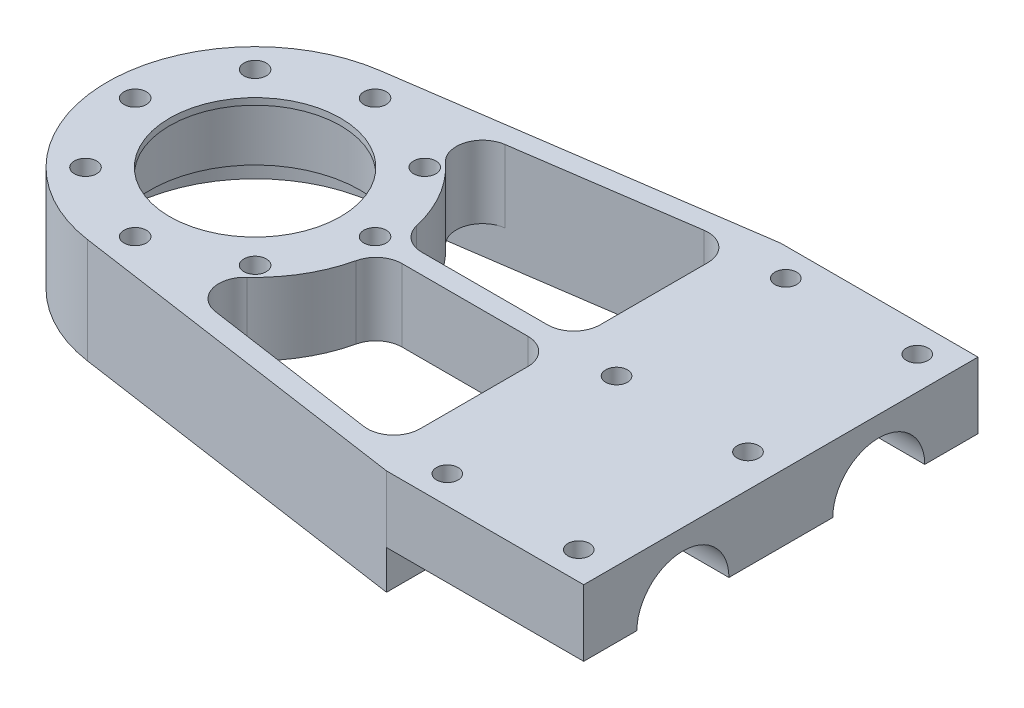
SolidWorks part; units mm, degrees
material "3.1355 (EN-AW 2024)"
ref_plane "Front" through (0, 0, 0) normal (0, 0, 1) x (1, 0, 0)
ref_plane "Top" through (0, 0, 0) normal (0, 1, 0) x (1, 0, 0)
ref_plane "Right" through (0, 0, 0) normal (1, 0, 0) x (0, 0, -1)
sketch "Эскиз1" plane through (0, 0, 0) normal (0, 1, 0) x (1, 0, 0)
  line L0 (0, 0) -> (0, 60)
  line L1 (0, 60) -> (-30, 60)
  line L2 (0, 30) -> (-130, 30) construction
  line L3 (-30, 60) -> (-30, 30) construction
  line L4 (-30, 60) -> (-83.2348, 52.2663)
  line L5 (-30, 0) -> (-83.2348, 7.7337)
  line L6 (0, 0) -> (-30, 0)
  circle A0 centre (-80, 30) radius 22.5 construction
  arc A1 (-83.2348, 52.2663) -> (-83.2348, 7.7337) centre (-80, 30) ccw
  dimension "D2" = 45
  dimension "D1" = 60
  dimension "D3" = 30
  dimension "D4" = 130
  dimension "D5" = 50
extrude "Бобышка-Вытянуть1" add sketch "Эскиз1" along normal blind 16
sketch "Эскиз2" plane through (0, 0, 0) normal (0, -1, 0) x (1, 0, 0)
  circle A0 centre (-80, -30) radius 16
  dimension "D1" = 32
extrude "Вырез-Вытянуть1" cut sketch "Эскиз2" against normal offset from surface (15 mm away) 1 up to face at (-40.9558, 16, -30)
sketch "Эскиз3" plane through (0, 15, 0) normal (0, -1, 0) x (1, 0, 0)
  circle A0 centre (-80, -30) radius 13
  dimension "D1" = 26
extrude "Вырез-Вытянуть2" cut sketch "Эскиз3" against normal through all
sketch "Эскиз4" plane through (0, 0, 0) normal (0, -1, 0) x (1, 0, 0)
  circle A0 centre (-80, -30) radius 20.5
  dimension "D1" = 41
extrude "Вырез-Вытянуть3" cut sketch "Эскиз4" against normal offset from surface (5 mm away) 10 up to face at (-80, 15, -43)
sketch "Эскиз5" plane through (0, 5, 0) normal (0, -1, 0) x (1, 0, 0)
  line L0 (-80, -30) -> (-98.25, -30) construction
  line L1 (-80, -30) -> (-92.9047, -17.0953) construction
  line L2 (-80, -30) -> (-67.0953, -17.0953) construction
  line L3 (-80, -30) -> (-67.0953, -42.9047) construction
  line L4 (-80, -30) -> (-92.9047, -42.9047) construction
  line L5 (-80, -30) -> (-80, -11.75) construction
  line L6 (-80, -30) -> (-61.75, -30) construction
  line L7 (-80, -30) -> (-80, -48.25) construction
  circle A0 centre (-80, -30) radius 18.25 construction
  circle A1 centre (-80, -30) radius 20.5 construction
  point P13 (-80, -30)
  point P17 (-80, -30)
  dimension "D1" = 36.5
  dimension "D2" = 45
  dimension "D3" = 4
  dimension "D4" = 4
hole_wizard "Отверстие с зазором M32" positions "Эскиз19" profile "Эскиз18" hole size "M3" standard "Ansi Metric" end condition through all
sketch "Эскиз19" plane through (0, 5, 0) normal (0, -1, 0) x (-1, 0, 0)
  point P0 (92.9047, 17.0953)
  point P3 (67.0953, 17.0953)
  point P6 (67.0953, 42.9047)
  point P9 (92.9047, 42.9047)
  point P12 (80, 11.75)
  point P15 (61.75, 30)
  point P18 (80, 48.25)
  point P21 (98.25, 30)
sketch "Эскиз18" plane through (-92.9047, 5, -17.0953) normal (1, 0, 0) x (0, 0, -1)
  line L0 (0, 0) -> (0, 11)
  line L1 (0, 11) -> (1.7, 11)
  line L2 (1.7, 11) -> (1.7, 0)
  line L5 (1.7, 0) -> (0, 0)
  line L11 (0, -6.35) -> (0, 107.95) construction
  dimension "Диаметр сквозного отверстия" = 3.4
  dimension "Глубина сквозного отверстия" = 11
sketch "Эскиз8" plane through (0, 0, 0) normal (1, 0, 0) x (0, 0, -1)
  line L0 (30, 16) -> (30, 0) construction
  line L1 (8.1, 5.9) -> (0, 5.9)
  line L2 (0, 16) -> (60, 16) construction
  line L3 (51.9, 5.9) -> (60, 5.9)
  line L4 (22.1, 5.9) -> (37.9, 5.9)
  line L5 (52.5, 0) -> (7.5, 0) construction
  line L6 (0, 16) -> (0, 0) construction
  line L7 (48.667, 0) -> (60, 0)
  line L8 (18.867, 0) -> (41.133, 0)
  line L18 (0, 0) -> (60, 0)
  line L19 (60, 0) -> (60, 16)
  line L20 (60, 16) -> (0, 16)
  line L21 (0, 16) -> (0, 0)
  line L22 (0, 0) -> (11.333, 0)
  line L23 (60, 0) -> (60, 5.9)
  line L25 (0, 5.9) -> (0, 0)
  circle A0 centre (15.1, 5.9) radius 7
  circle A1 centre (44.9, 5.9) radius 7
  line M3 (0, 0) -> (60, 0)
  line M4 (60, 0) -> (60, 16)
  line M6 (0, 16) -> (0, 0)
  dimension "D1" = 14
  dimension "D3" = 10.1
  dimension "D4" = 0
  dimension "D2" = 15.1
extrude "Вырез-Вытянуть8" cut sketch "Эскиз8" against normal blind 30 contours A0 M3 | A0 L1 M6 M3 | L4 L0 L8 A1 | A1 M3 | L3 A1 M3 M4 | L0 L4 A0 M3 region at (0, 2.7829, -34.4738) region at (0, 2.7829, -25.5262) region at (0, 6.1403, -15.1) region at (0, 6.1403, -44.9) region at (0, 2.7866, -55.4273) region at (0, 2.7866, -4.5727)
sketch "Эскиз12" plane through (0, 0, 0) normal (0, -1, 0) x (1, 0, 0)
  line L0 (-30, 0) -> (-83.2348, -7.7337) construction
  line L1 (-30, -60) -> (-83.2348, -52.2663) construction
  line L2 (-30, -60) -> (-30, -30) construction
  line L3 (-30, 0) -> (-76.5229, -6.7587)
  line L4 (-30, -60) -> (-76.5229, -53.2413)
  line L5 (-30, -60) -> (-30, 0)
  circle A2 centre (-80, -30) radius 23.5
  arc A3 (-76.5229, -53.2413) -> (-76.5229, -6.7587) centre (-80, -30) ccw
  dimension "D1" = 3
extrude "Вырез-Вытянуть9" [suppressed] cut sketch "Эскиз12" against normal up to surface (5.9 mm away) up to face at (-15, 5.9, -4.05)
sketch "Эскиз13" [suppressed] plane through (0, 3.1366, 0) normal (0, -1, 0) x (1, 0, 0)
  line L4 (-27, -24.6401) -> (-27, -35.3599)
  line L5 (-27, -24.6401) -> (-27, -35.3599)
  line L26 (-3, -35.3599) -> (-3, -24.6401)
  line L27 (-3, -24.6401) -> (-27, -24.6401)
  line L36 (-27, -35.3599) -> (-3, -35.3599)
  arc A0 (-76.5229, -53.2413) -> (-76.5229, -6.7587) centre (-80, -30) ccw construction
  arc A1 (-69.8248, -51.1829) -> (-69.8248, -8.8171) centre (-80, -30) ccw
  dimension "D1" = 3
extrude "Вырез-Вытянуть10" [suppressed] cut sketch "Эскиз13" against normal through all
sketch "Эскиз14" plane through (0, 0, 0) normal (0, -1, 0) x (1, 0, 0)
  line L9 (-33, -56.5327) -> (-82.8035, -49.2974)
  line L10 (-33, -3.4673) -> (-33, -56.5327)
  line L11 (-82.8035, -10.7026) -> (-33, -3.4673)
  line L12 (-33, -56.5327) -> (-76.5446, -50.2067)
  line L13 (-33, -3.4673) -> (-33, -56.5327)
  line L14 (-76.5446, -9.7933) -> (-33, -3.4673)
  circle A0 centre (-80, -30) radius 20.5 construction
  arc A1 (-76.5446, -50.2067) -> (-76.5446, -9.7933) centre (-80, -30) ccw
  dimension "D1" = 3
extrude "Вырез-Вытянуть11" cut sketch "Эскиз14" against normal through all
sketch "Эскиз15" plane through (0, 5, 0) normal (0, -1, 0) x (1, 0, 0)
  line L0 (-59.5, -30) -> (-33, -30) construction
  line L1 (-33, -56.5327) -> (-33, -3.4673) construction
  line L2 (-59.555, -31.5) -> (-33, -31.5)
  line L3 (-59.555, -28.5) -> (-33, -28.5)
  line L4 (-59.5, -28.5) -> (-33, -28.5) construction
  line L5 (-59.5, -31.5) -> (-33, -31.5) construction
  line L6 (-33, -28.5) -> (-33, -31.5)
  arc A0 (-76.5446, -50.2067) -> (-76.5446, -9.7933) centre (-80, -30) ccw construction
  arc A1 (-59.555, -31.5) -> (-59.555, -28.5) centre (-80, -30) ccw
  dimension "D1" = 1.5
  dimension "D2" = 1.5
extrude "Бобышка-Вытянуть2" add sketch "Эскиз15" against normal through all
fillet "Скругление1" radius 4 8 edges at (-33, 8, -3.4673) (-76.5446, 10.5, -9.7933) (-33, 10.5, -28.5) (-59.555, 10.5, -28.5) (-33, 8, -56.5327) (-33, 10.5, -31.5) (-59.555, 10.5, -31.5) (-76.5446, 10.5, -50.2067)
hole_wizard "Отверстие обработанное метчиком M4x0.71" positions "Эскиз23" profile "Эскиз24" tap size "M4x0.7" standard "Ansi Metric" end condition through all
sketch "Эскиз23" plane through (-72.5396, 5.9, -28.0043) normal (0, -1, 0) x (-0.7071, 0, 0.7071)
  point P0 (-67.3769, -28.1386)
  point P3 (-53.2348, -13.9964)
  point P6 (-35.0268, -32.2044)
  point P9 (-49.1689, -46.3466)
  point P12 (-30.9609, -64.5546)
  point P15 (-16.8188, -50.4124)
sketch "Эскиз24" plane through (-5, 5.9, -55.75) normal (1, 0, 0) x (0, 0, -1)
  line L0 (0, 0) -> (0, 10.1)
  line L1 (0, 10.1) -> (1.65, 10.1)
  line L2 (1.65, 10.1) -> (1.65, 0)
  line L3 (1.65, 0) -> (0, 0)
  line L4 (0, -6.35) -> (0, 107.95) construction
  dimension "Диаметр проходного сверла" = 3.3
  dimension "Глубина проходного сверла" = 10.1
cosmetic thread "Отверстие резьбы11" parameters "D2"=4
cosmetic thread "Отверстие резьбы12" parameters "D2"=4
cosmetic thread "Отверстие резьбы13" parameters "D2"=4
cosmetic thread "Отверстие резьбы14" parameters "D2"=4
cosmetic thread "Отверстие резьбы15" parameters "D2"=4
cosmetic thread "Отверстие резьбы16" parameters "D2"=4
equation "\"D4@Эскиз1\"=\"D3@Эскиз1\"+100"
equation "\"D1@Эскиз5\"=32+4.5"
